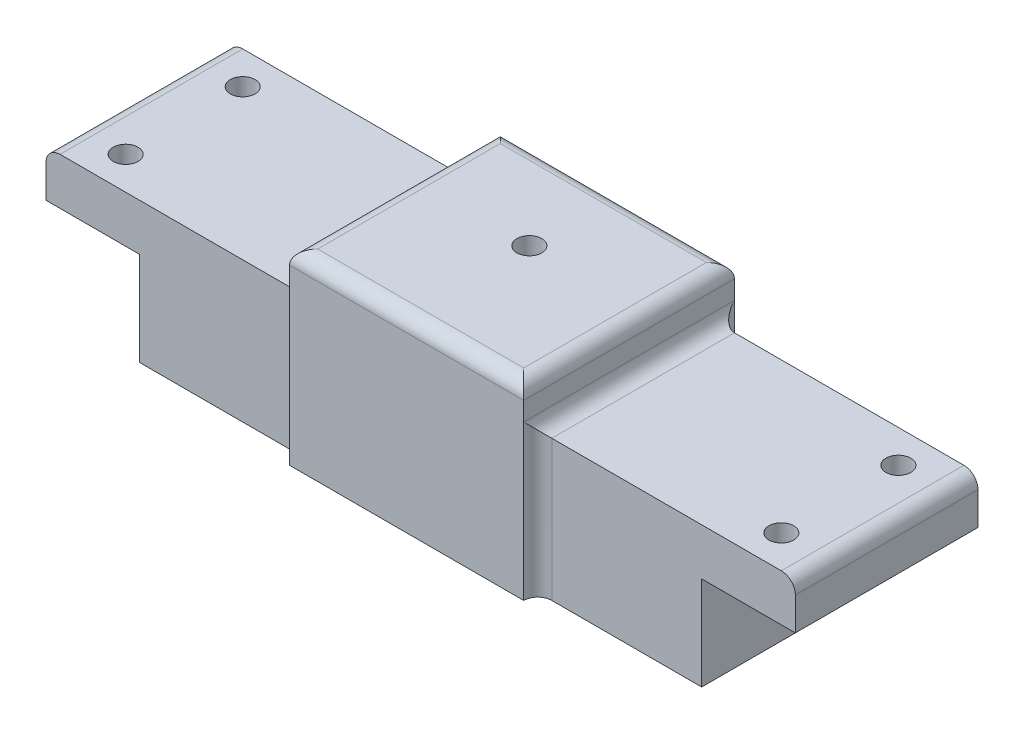
SolidWorks part; units mm, degrees
material "PLA"
ref_plane "前视基准面" through (0, 0, 0) normal (0, 0, 1) x (1, 0, 0)
ref_plane "上视基准面" through (0, 0, 0) normal (0, 1, 0) x (1, 0, 0)
ref_plane "右视基准面" through (0, 0, 0) normal (1, 0, 0) x (0, 0, -1)
sketch "草图1" plane through (0, 0, 0) normal (0, 0, 1) x (1, 0, 0)
  line L0 (0, 0) -> (0, -74.9741) construction
  line L1 (25, 0) -> (-25, 0)
  line L2 (-25, 0) -> (-25, -10)
  line L3 (-25, -10) -> (-80, -10)
  line L4 (-80, -10) -> (-80, -20)
  line L5 (-80, -20) -> (-60, -20)
  line L6 (-60, -20) -> (-60, -40)
  line L7 (-60, -40) -> (60, -40)
  line L8 (60, -20) -> (60, -40)
  line L9 (80, -20) -> (60, -20)
  line L10 (25, -10) -> (80, -10)
  line L11 (25, 0) -> (25, -10)
  line L12 (80, -10) -> (80, -20)
  point P11 (0, -40)
  dimension "D1" = 160
  dimension "D2" = 120
  dimension "D3" = 50
  dimension "D4" = 40
  dimension "D5" = 20
  dimension "D6" = 10
extrude "凸台-拉伸1" add sketch "草图1" along normal blind 45
sketch "草图2" plane through (0, 0, 0) normal (0, 0, -1) x (-1, 0, 0)
  line L0 (60, -40) -> (-60, -40) construction
  line L1 (-15, -40) -> (15, -40)
  line L2 (-15, -40) -> (-15, -5)
  line L3 (-15, -5) -> (15, -5)
  line L4 (15, -40) -> (15, -5)
  line L5 (0, -5) -> (0, -40) construction
  line L6 (-15, -22.5) -> (15, -22.5) construction
  point P72 (0, -22.5)
  dimension "D1" = 30
  dimension "D2" = 35
extrude "切除-拉伸1" cut sketch "草图2" against normal blind 40.5
sketch "草图4" plane through (0, -5, 0) normal (0, -1, 0) x (1, 0, 0)
  line L0 (0, 0) -> (0, 34.7086) construction
  line L1 (15, 40.5) -> (-15, 40.5) construction
  circle A0 centre (0, 18.8) radius 2.65
  dimension "D1" = 5.3
  dimension "D2" = 21.7
extrude "切除-拉伸2" cut sketch "草图4" against normal blind 40
sketch "草图5" plane through (0, -40, 0) normal (0, -1, 0) x (1, 0, 0)
  line L0 (0, 0) -> (0, 69.1908) construction
  line L1 (-55, 37) -> (-20, 37)
  line L2 (-55, 37) -> (-55, 8)
  line L3 (-55, 8) -> (-20, 8)
  line L4 (-20, 37) -> (-20, 8)
  line L5 (-37.5, 8) -> (-37.5, 37) construction
  line L6 (-55, 22.5) -> (-20, 22.5) construction
  line L7 (-60, 45) -> (-60, 0) construction
  line L8 (-60, 45) -> (60, 45) construction
  line L9 (-15, 40.5) -> (-15, 0) construction
  line L10 (-60, 0) -> (-15, 0) construction
  line L11 (55, 8) -> (20, 8)
  line L12 (20, 37) -> (20, 8)
  line L13 (55, 37) -> (20, 37)
  line L14 (55, 37) -> (55, 8)
  point P104 (-37.5, 22.5)
  dimension "D1" = 5
  dimension "D2" = 8
  dimension "D3" = 5
  dimension "D4" = 8
extrude "切除-拉伸3" cut sketch "草图5" against normal blind 25
sketch "草图6" plane through (0, -10, 0) normal (0, 1, 0) x (1, 0, 0)
  line L0 (70, 0) -> (70, -45) construction
  line L1 (80, 0) -> (25, 0) construction
  line L2 (80, -45) -> (25, -45) construction
  line L3 (0, 0) -> (0, -83.6514) construction
  line L4 (80, -45) -> (80, 0) construction
  line L5 (80, -22.5) -> (37.0042, -22.5) construction
  circle A0 centre (70, -10) radius 2.65
  circle A1 centre (70, -35) radius 2.65
  circle A2 centre (-70, -35) radius 2.65
  circle A3 centre (-70, -10) radius 2.65
  dimension "D2" = 25
  dimension "D3" = 5.3
  dimension "D1" = 10
extrude "切除-拉伸4" cut sketch "草图6" against normal through all
sketch "草图7" plane through (0, -10, 0) normal (0, 1, 0) x (1, 0, 0)
  line L0 (-25, -45) -> (-25, 0) construction
  line L1 (-80, 0) -> (-25, 0)
  line L2 (-80, 0) -> (-80, -3)
  line L3 (-80, -3) -> (-25, -3)
  line L4 (-25, 0) -> (-25, -3)
  line L5 (-52.5, -3) -> (-52.5, 0) construction
  line L6 (-80, -1.5) -> (-25, -1.5) construction
  line L7 (0, 21.4981) -> (0, -18.8) construction
  line L8 (-80, -22.5) -> (33.6156, -22.5) construction
  line L9 (-80, -45) -> (-80, 0) construction
  line L10 (-80, -42) -> (-25, -42)
  line L11 (-25, -45) -> (-25, -42)
  line L12 (-80, -45) -> (-25, -45)
  line L13 (-80, -45) -> (-80, -42)
  line L14 (80, -45) -> (80, -42)
  line L15 (80, -45) -> (25, -45)
  line L16 (25, -45) -> (25, -42)
  line L17 (80, -42) -> (25, -42)
  line L18 (80, -3) -> (25, -3)
  line L19 (25, 0) -> (25, -3)
  line L20 (80, 0) -> (25, 0)
  line L21 (80, 0) -> (80, -3)
  point P128 (-52.5, -1.5)
  dimension "D1" = 3
extrude "切除-拉伸5" cut sketch "草图7" against normal through all
fillet "圆角1" radius 3 28 edges at (80, -10, 22.5) (-80, -10, 22.5) (0, 0, 0) (-25, 0, 22.5) (0, 0, 45) (25, 0, 22.5) (25, -25, 42) (-25, -25, 42) (-25, -10, 22.5) (-25, -25, 3) (25, -25, 3) (25, -10, 22.5) (-37.5, -15, 37) (-20, -15, 22.5) (-37.5, -15, 8) (-55, -15, 22.5) (-55, -27.5, 37) (-20, -27.5, 37) (-20, -27.5, 8) (-55, -27.5, 8) (20, -27.5, 37) (37.5, -15, 37) (55, -27.5, 37) (55, -15, 22.5) (20, -15, 22.5) (20, -27.5, 8) (55, -27.5, 8) (37.5, -15, 8)
